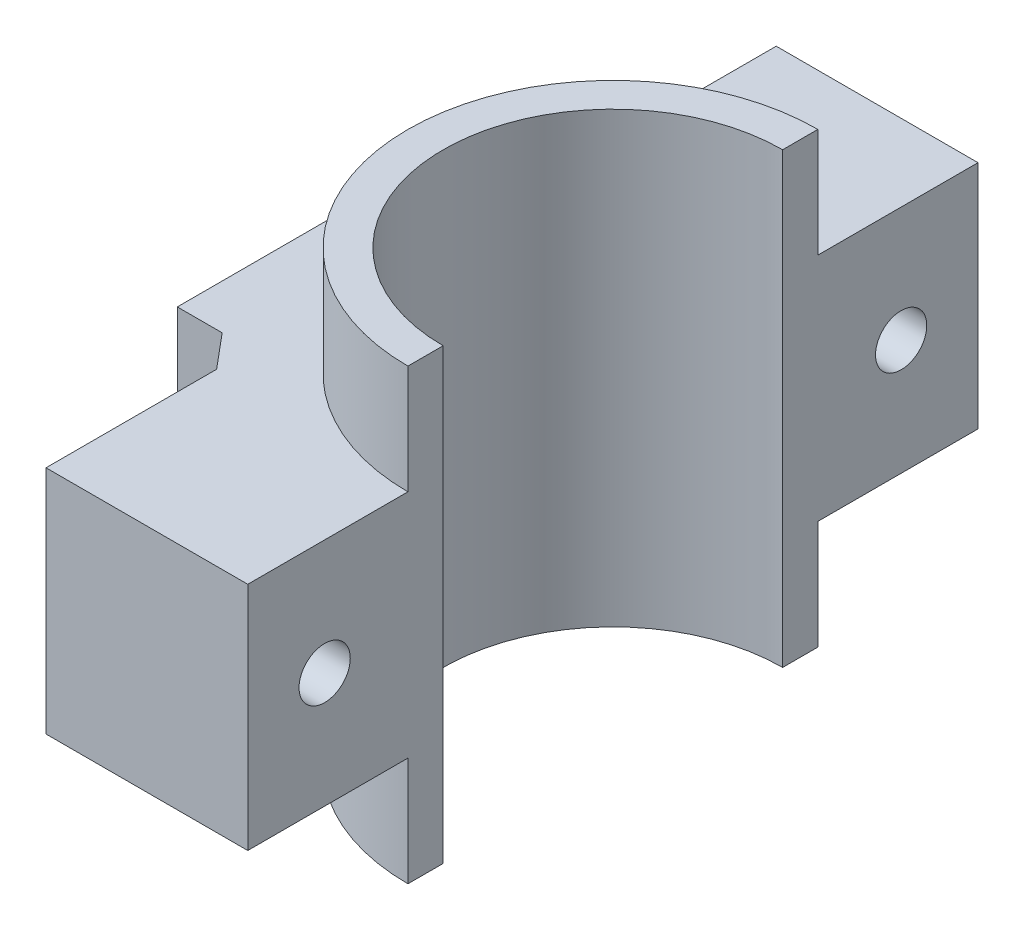
SolidWorks part; units mm, degrees
ref_plane "Front Plane" through (0, 0, 0) normal (0, 0, 1) x (1, 0, 0)
ref_plane "Top Plane" through (0, 0, 0) normal (0, 1, 0) x (1, 0, 0)
ref_plane "Right Plane" through (0, 0, 0) normal (1, 0, 0) x (0, 0, -1)
sketch "Sketch1" plane through (0, 0, 0) normal (0, 1, 0) x (1, 0, 0)
  line L0 (-89.3059, 0) -> (80.5868, 0) construction
  line L1 (0, 22.9525) -> (0, -27.5437) construction
  line L2 (0, 26.5) -> (0, 32)
  line L3 (-43, -25) -> (-43, 25)
  line L4 (-43, 25) -> (-36, 25)
  line L5 (-36, 25) -> (-31.5005, 30.3623)
  line L6 (0, 57) -> (-31.5005, 57)
  line L7 (-31.5005, 57) -> (-31.5005, 30.3623)
  line L8 (0, 32) -> (0, 57)
  line L9 (-43, -25) -> (-36, -25)
  line L10 (-36, -25) -> (-31.5005, -30.3623)
  line L11 (-31.5005, -57) -> (-31.5005, -30.3623)
  line L12 (0, -57) -> (-31.5005, -57)
  line L13 (0, -32) -> (0, -57)
  line L14 (0, -26.5) -> (0, -32)
  arc A0 (0, -26.5) -> (0, 26.5) centre (0, 0) cw
  arc A1 (0, -32) -> (0, 32) centre (0, 0) cw
  point P17 (-43, 0)
  dimension "D1" = 26.5
  dimension "D5" = 32
  dimension "D2" = 30.5
  dimension "D3" = 25
  dimension "D4" = 43
  dimension "D6" = 7
  dimension "D7" = 7
  dimension "D8" = 31.5005
  dimension "D9" = 5.5
  dimension "D10" = 25
extrude "Boss-Extrude1" add sketch "Sketch1" along normal mid plane 36 contours L13 A1 L8 L6 L7 L5 L4 L3 L9 L10 L11 L12 region at (-33.2184, 0, 0)
extrude "Boss-Extrude2" add sketch "Sketch1<3>" along normal mid plane 70 contours A1 L14 A0 L2 region at (-27.2155, 0, 0)
sketch "Sketch1<3>" plane through (0, 0, 0) normal (0, 1, 0) x (1, 0, 0) same geometry as "Sketch1"
sketch "Sketch2" plane through (0, 0, 0) normal (1, 0, 0) x (0, 0, -1)
  line L0 (0, 0) -> (-57, 0) construction
  line L1 (-57, 18) -> (-57, -18) construction
  circle A0 centre (-45, 0) radius 4
  dimension "D1" = 8
  dimension "D2" = 45
extrude "Cut-Extrude1" cut sketch "Sketch2" against normal up to next
mirror "Mirror1" about plane through (0, 0, 0) normal (0, 0, 1) of "Cut-Extrude1"
